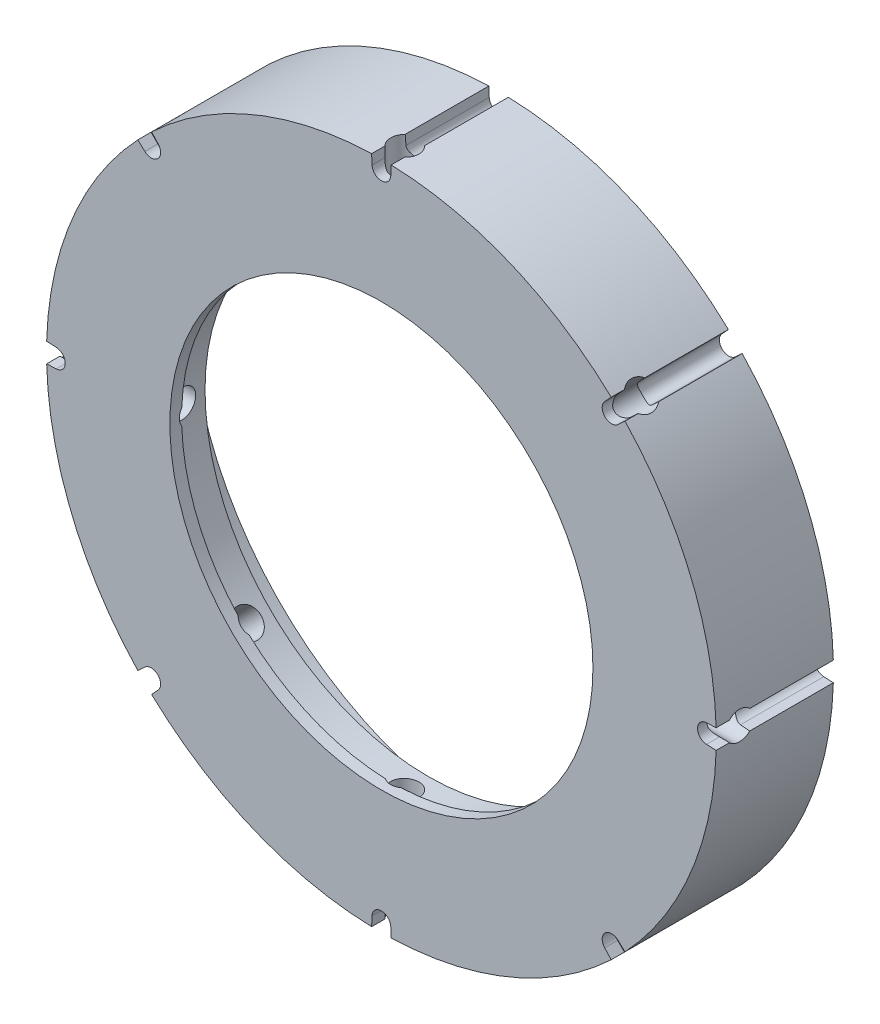
SolidWorks part; units mm, degrees
ref_plane "Front Plane" through (0, 0, 0) normal (0, 0, 1) x (1, 0, 0)
ref_plane "Top Plane" through (0, 0, 0) normal (0, 1, 0) x (1, 0, 0)
ref_plane "Right Plane" through (0, 0, 0) normal (1, 0, 0) x (0, 0, -1)
sketch "Sketch1" plane through (0, 0, 0) normal (0, 0, 1) x (1, 0, 0)
  circle A4 centre (0, 0) radius 14.2875
  circle A5 centre (0, 0) radius 13.15
  circle A6 centre (0, 0) radius 13.15
  dimension "D1" = 0.15
  dimension "D3" = 1.1375
  dimension "D2" = 28.575
extrude "Boss-Extrude1" add sketch "Sketch1" against normal blind 3
sketch "Sketch2" plane through (0, 0, 0) normal (0, 0, 1) x (1, 0, 0)
  circle A0 centre (0, 0) radius 14.2875
  circle A1 centre (0, 0) radius 9.025
  circle A2 centre (0, 0) radius 14.2875 construction
  dimension "D1" = 18.05
extrude "Boss-Extrude2" add sketch "Sketch2" along normal blind 2
sketch "Sketch3" plane through (0, 0, 2) normal (0, 0, 1) x (1, 0, 0)
  circle A0 centre (0, 0) radius 13.15 construction
  circle A1 centre (0, 0) radius 14.2875
  circle A2 centre (0, 0) radius 14.2875
  circle A3 centre (0, 0) radius 13.15
  dimension "D1" = 0
sketch "Sketch4" plane through (0, 0, 0) normal (0, 0, -1) x (-1, 0, 0)
  circle A1 centre (0, 0) radius 9.525
extrude "Cut-Extrude2" cut sketch "Sketch4" against normal blind 1.5
sketch "Sketch5" plane through (0, 0, -3) normal (0, 0, -1) x (-1, 0, 0)
  line L0 (-13.8709, 0.3997) -> (-14.2814, 0.4167)
  line L1 (-13.8709, -0.3997) -> (-14.2814, -0.4167)
  circle A3 centre (0, 0) radius 14.2875 construction
  circle A5 centre (0, 0) radius 14.2875
  circle A6 centre (-13.8875, 0) radius 0.4
  circle M4 centre (0, 0) radius 14.2875
extrude "Cut-Extrude4" cut sketch "Sketch5" against normal through all contours A6 | A6 L0 M4 | A6 A5 L1 region at (14.1918, 0.3195, -3) region at (13.8875, 0, -3) region at (14.1918, -0.3195, -3)
ref_plane "Plane1" through (14.2814, 0, 0) normal (1, 0, 0) x (0, 0, -1)
sketch "Sketch6" plane through (14.2814, 0, 0) normal (1, 0, 0) x (0, 0, -1)
  line L0 (-2, 0.4167) -> (3, 0.4167) construction
  line L1 (-2, 0.4167) -> (3, 0.4167)
  circle A0 centre (-1, 0) radius 0.6
extrude "Cut-Extrude5" cut sketch "Sketch6" against normal blind 10 contours L1 A0 | L1 A0 region at (14.2814, 0.4911, 1) region at (14.2814, -0.0525, 1)
sketch "Sketch7" plane through (0, 0, 0) normal (0, 1, 0) x (1, 0, 0)
  line L0 (0, 0) -> (0, 6.608) construction
pattern_circular "CirPattern1" count 8 over 360 about axis through (0, 0, 0) along (0, 0, -1) of "Cut-Extrude5", "Cut-Extrude4"
ref_axis "Axis1" through (0, -8.985, 1) along (0, -1, 0)
ref_plane "Plane2" through (-0.3317, -9.5192, 1.5) normal (0, -1, 0) x (-1, 0, 0)
ref_point "Point1"
